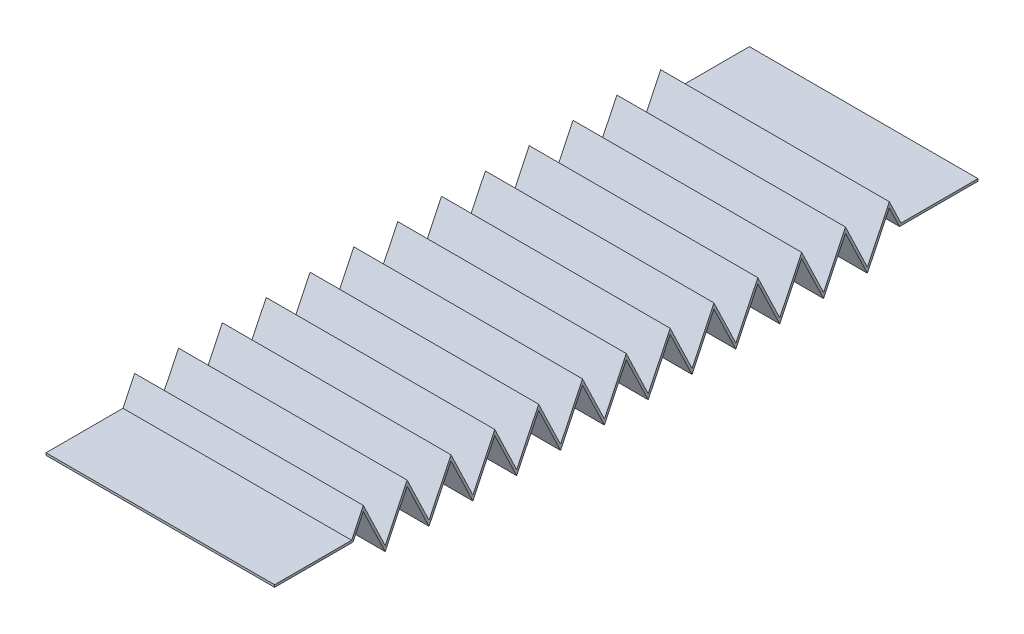
SolidWorks part; units mm, degrees
ref_plane "Front Plane" through (0, 0, 0) normal (0, 0, 1) x (1, 0, 0)
ref_plane "Top Plane" through (0, 0, 0) normal (0, 1, 0) x (1, 0, 0)
ref_plane "Right Plane" through (0, 0, 0) normal (1, 0, 0) x (0, 0, -1)
sketch "Sketch2" plane through (0, 0, 0) normal (0, 0, 1) x (1, 0, 0)
  line L1 (-27.5, 10) -> (27.5, 10)
  line L2 (-27.5, 10) -> (-27.5, 0)
  line L3 (-27.5, 0) -> (27.5, 0)
  line L4 (27.5, 10) -> (27.5, 0)
  point P4 (0, 0)
  dimension "D1" = 10
  dimension "D2" = 55
sketch "Sketch3" plane through (0, 0, 0) normal (1, 0, 0) x (0, 0, -1)
  line L0 (0, 10) -> (153.8422, 10) construction
  line L1 (0, 0) -> (153.8422, 0) construction
  line L3 (17, 5) -> (19.3968, 10)
  line L4 (19.3968, 10) -> (24.1905, 0)
  line L5 (24.1905, 0) -> (28.9842, 10)
  line L6 (28.9842, 10) -> (33.7779, 0)
  line L7 (33.7779, 0) -> (38.5716, 10)
  line L8 (38.5716, 10) -> (43.3653, 0)
  line L9 (43.3653, 0) -> (48.159, 10)
  line L10 (48.159, 10) -> (52.9527, 0)
  line L11 (52.9527, 0) -> (57.7464, 10)
  line L12 (57.7464, 10) -> (62.5401, 0)
  line L13 (62.5401, 0) -> (67.3337, 10)
  line L14 (67.3337, 10) -> (72.1274, 0)
  line L15 (72.1274, 0) -> (76.9211, 10)
  line L16 (76.9211, 10) -> (81.7148, 0)
  line L17 (81.7148, 0) -> (86.5085, 10)
  line L18 (86.5085, 10) -> (91.3022, 0)
  line L19 (0, 10) -> (0, 0) construction
  line L20 (91.3022, 0) -> (96.0959, 10)
  line L21 (96.0959, 10) -> (100.8896, 0)
  line L22 (100.8896, 0) -> (105.6833, 10)
  line L23 (105.6833, 10) -> (110.477, 0)
  line L24 (110.477, 0) -> (115.2706, 10)
  line L25 (115.2706, 10) -> (120.0643, 0)
  line L26 (120.0643, 0) -> (124.858, 10)
  line L27 (124.858, 10) -> (129.6517, 0)
  line L28 (129.6517, 0) -> (134.4454, 10)
  line L29 (134.4454, 10) -> (136.8422, 5)
  line L30 (153.8422, 10) -> (153.8422, 0) construction
  line L31 (17, 5) -> (0, 5)
  line L32 (136.8422, 5) -> (153.8422, 5)
  line L33 (153.8422, -12.75) -> (153.8422, -19.8536) construction
  dimension "D2" = 17
  dimension "D1" = 10
  dimension "D3" = 17
extrude "Extrude-Thin1" add sketch "Sketch3" against normal mid plane 50 thin thin type mid plane wall 0.5
